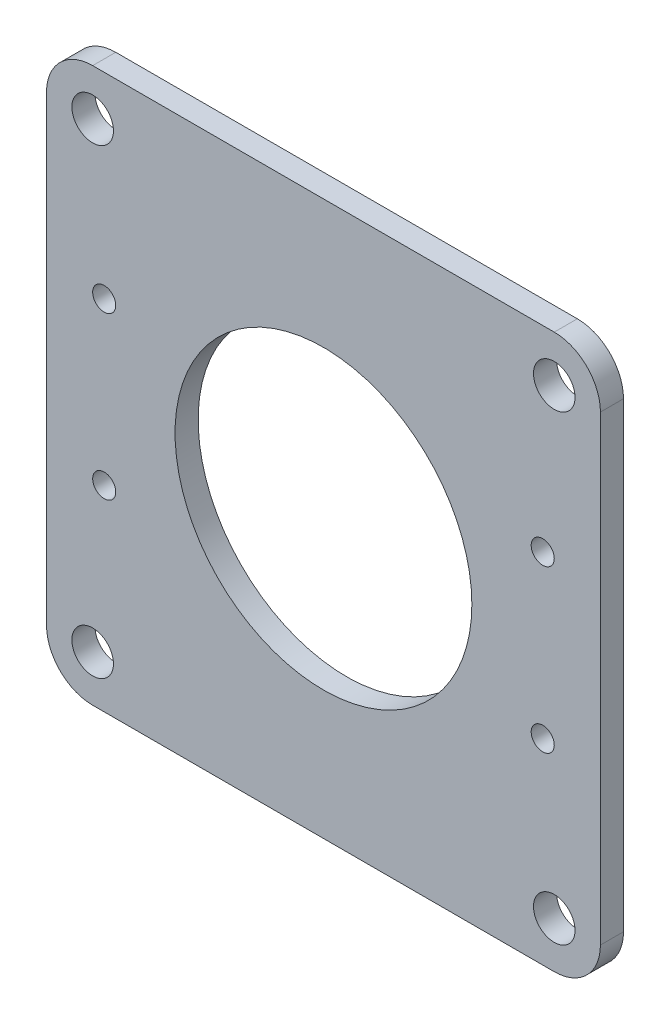
SolidWorks part; units mm, degrees
ref_plane "Front Plane" through (0, 0, 0) normal (0, 0, 1) x (1, 0, 0)
ref_plane "Top Plane" through (0, 0, 0) normal (0, 1, 0) x (1, 0, 0)
ref_plane "Right Plane" through (0, 0, 0) normal (1, 0, 0) x (0, 0, -1)
sketch "Model" plane through (0, 0, 0) normal (0, 0, 1) x (1, 0, 0)
  line L0 (80.983, 843.7421) -> (65.983, 843.7421)
  line L1 (30.983, 843.7421) -> (30.983, 993.7421)
  line L2 (45.983, 993.7421) -> (30.983, 993.7421)
  line L3 (47.983, 998.7421) -> (45.983, 996.7421)
  line L4 (47.983, 998.7421) -> (63.983, 998.7421)
  line L5 (65.983, 996.7421) -> (65.983, 993.7421)
  line L6 (45.983, 993.7421) -> (45.983, 996.7421)
  line L7 (45.983, 843.7421) -> (30.983, 843.7421)
  line L8 (80.983, 843.7421) -> (80.983, 993.7421)
  line L9 (65.983, 996.7421) -> (63.983, 998.7421)
  line L10 (80.983, 993.7421) -> (65.983, 993.7421)
  line L11 (65.983, 835.7421) -> (65.983, 843.7421)
  line L12 (45.983, 835.7421) -> (47.983, 833.7421)
  line L13 (63.983, 833.7421) -> (65.983, 835.7421)
  line L14 (63.983, 833.7421) -> (47.983, 833.7421)
  line L15 (45.983, 843.7421) -> (45.983, 835.7421)
  line L16 (63.4792, 562.0753) -> (47.4792, 562.0753)
  line L17 (45.4792, 564.0753) -> (47.4792, 562.0753)
  line L18 (45.4792, 572.0753) -> (45.4792, 564.0753)
  line L19 (80.4792, 572.0753) -> (65.4792, 572.0753)
  line L20 (45.4792, 572.0753) -> (30.4792, 572.0753)
  line L21 (80.4792, 572.0753) -> (80.4792, 722.0753)
  line L22 (65.4792, 725.0753) -> (63.4792, 727.0753)
  line L23 (65.4792, 725.0753) -> (65.4792, 722.0753)
  line L24 (80.4792, 722.0753) -> (65.4792, 722.0753)
  line L25 (45.4792, 722.0753) -> (30.4792, 722.0753)
  line L26 (45.4792, 722.0753) -> (45.4792, 725.0753)
  line L27 (63.4792, 562.0753) -> (65.4792, 564.0753)
  line L28 (30.4792, 572.0753) -> (30.4792, 722.0753)
  line L29 (47.4792, 727.0753) -> (45.4792, 725.0753)
  line L30 (47.4792, 727.0753) -> (63.4792, 727.0753)
  line L31 (65.4792, 564.0753) -> (65.4792, 572.0753)
  line L32 (-372.5225, 514.5401) -> (-370.5225, 512.5401)
  line L33 (-316.5225, 514.5401) -> (-314.5225, 512.5401)
  line L34 (-290.5225, 512.5401) -> (-288.5225, 514.5401)
  line L35 (-234.5225, 512.5401) -> (-232.5225, 514.5401)
  line L36 (-260.5225, 514.5401) -> (-258.5225, 512.5401)
  line L37 (-314.5225, 512.5401) -> (-290.5225, 512.5401)
  line L38 (-370.5225, 512.5401) -> (-346.5225, 512.5401)
  line L39 (-258.5225, 512.5401) -> (-234.5225, 512.5401)
  line L40 (-232.5225, 675.5401) -> (-234.5225, 677.5401)
  line L41 (-258.5225, 677.5401) -> (-260.5225, 675.5401)
  line L42 (-288.5225, 675.5401) -> (-290.5225, 677.5401)
  line L43 (-314.5225, 677.5401) -> (-316.5225, 675.5401)
  line L44 (-344.5225, 675.5401) -> (-346.5225, 677.5401)
  line L45 (-370.5225, 677.5401) -> (-372.5225, 675.5401)
  line L46 (-234.5225, 677.5401) -> (-258.5225, 677.5401)
  line L47 (-346.5225, 677.5401) -> (-370.5225, 677.5401)
  line L48 (-290.5225, 677.5401) -> (-314.5225, 677.5401)
  line L49 (-316.5225, 522.5401) -> (-316.5225, 514.5401)
  line L50 (-288.5225, 514.5401) -> (-288.5225, 522.5401)
  line L51 (-260.5225, 522.5401) -> (-260.5225, 514.5401)
  line L52 (-344.5225, 514.5401) -> (-344.5225, 522.5401)
  line L53 (-260.5225, 672.5401) -> (-288.5225, 672.5401)
  line L54 (-316.5225, 672.5401) -> (-344.5225, 672.5401)
  line L55 (-344.5225, 522.5401) -> (-316.5225, 522.5401)
  line L56 (-288.5225, 522.5401) -> (-260.5225, 522.5401)
  line L57 (-288.5225, 672.5401) -> (-288.5225, 675.5401)
  line L58 (-316.5225, 675.5401) -> (-316.5225, 672.5401)
  line L59 (-344.5225, 672.5401) -> (-344.5225, 675.5401)
  line L60 (-260.5225, 675.5401) -> (-260.5225, 672.5401)
  line L61 (-232.5225, 514.5401) -> (-232.5225, 675.5401)
  line L62 (-372.5225, 675.5401) -> (-372.5225, 514.5401)
  line L63 (-346.5225, 512.5401) -> (-344.5225, 514.5401)
  line L64 (-59.6771, 563.4465) -> (-59.6771, 571.4465)
  line L65 (-85.6771, 561.4465) -> (-61.6771, 561.4465)
  line L66 (-87.6771, 571.4465) -> (-87.6771, 563.4465)
  line L67 (-115.6771, 571.4465) -> (-87.6771, 571.4465)
  line L68 (-115.6771, 563.4465) -> (-115.6771, 571.4465)
  line L69 (-141.6771, 561.4465) -> (-117.6771, 561.4465)
  line L70 (-143.6771, 724.4465) -> (-143.6771, 563.4465)
  line L71 (-141.6771, 726.4465) -> (-143.6771, 724.4465)
  line L72 (-117.6771, 726.4465) -> (-141.6771, 726.4465)
  line L73 (-115.6771, 724.4465) -> (-117.6771, 726.4465)
  line L74 (-115.6771, 721.4465) -> (-115.6771, 724.4465)
  line L75 (-87.6771, 721.4465) -> (-115.6771, 721.4465)
  line L76 (-87.6771, 724.4465) -> (-87.6771, 721.4465)
  line L77 (-85.6771, 726.4465) -> (-87.6771, 724.4465)
  line L78 (-61.6771, 726.4465) -> (-85.6771, 726.4465)
  line L79 (-59.6771, 724.4465) -> (-61.6771, 726.4465)
  line L80 (-59.6771, 721.4465) -> (-59.6771, 724.4465)
  line L81 (-31.6771, 721.4465) -> (-59.6771, 721.4465)
  line L82 (-31.6771, 724.4465) -> (-31.6771, 721.4465)
  line L83 (-29.6771, 726.4465) -> (-31.6771, 724.4465)
  line L84 (-5.6771, 726.4465) -> (-29.6771, 726.4465)
  line L85 (-3.6771, 724.4465) -> (-5.6771, 726.4465)
  line L86 (-3.6771, 563.4465) -> (-3.6771, 724.4465)
  line L87 (-5.6771, 561.4465) -> (-3.6771, 563.4465)
  line L88 (-29.6771, 561.4465) -> (-5.6771, 561.4465)
  line L89 (-31.6771, 563.4465) -> (-29.6771, 561.4465)
  line L90 (-31.6771, 571.4465) -> (-31.6771, 563.4465)
  line L91 (-59.6771, 571.4465) -> (-31.6771, 571.4465)
  line L92 (-117.6771, 561.4465) -> (-115.6771, 563.4465)
  line L93 (-143.6771, 563.4465) -> (-141.6771, 561.4465)
  line L94 (-87.6771, 563.4465) -> (-85.6771, 561.4465)
  line L95 (-61.6771, 561.4465) -> (-59.6771, 563.4465)
  line L96 (-53.1392, 838.5777) -> (-53.1392, 846.5777)
  line L97 (-55.1392, 836.5777) -> (-53.1392, 838.5777)
  line L98 (-79.1392, 836.5777) -> (-55.1392, 836.5777)
  line L99 (-81.1392, 838.5777) -> (-79.1392, 836.5777)
  line L100 (-81.1392, 846.5777) -> (-81.1392, 838.5777)
  line L101 (-109.1392, 846.5777) -> (-81.1392, 846.5777)
  line L102 (-109.1392, 838.5777) -> (-109.1392, 846.5777)
  line L103 (-135.1392, 836.5777) -> (-111.1392, 836.5777)
  line L104 (-135.1392, 1001.5777) -> (-137.1392, 999.5777)
  line L105 (-111.1392, 1001.5777) -> (-135.1392, 1001.5777)
  line L106 (-109.1392, 999.5777) -> (-111.1392, 1001.5777)
  line L107 (-81.1392, 996.5777) -> (-109.1392, 996.5777)
  line L108 (-81.1392, 999.5777) -> (-81.1392, 996.5777)
  line L109 (-79.1392, 1001.5777) -> (-81.1392, 999.5777)
  line L110 (-55.1392, 1001.5777) -> (-79.1392, 1001.5777)
  line L111 (-53.1392, 999.5777) -> (-55.1392, 1001.5777)
  line L112 (-53.1392, 996.5777) -> (-53.1392, 999.5777)
  line L113 (-25.1392, 996.5777) -> (-53.1392, 996.5777)
  line L114 (-23.1392, 1001.5777) -> (-25.1392, 999.5777)
  line L115 (0.8608, 1001.5777) -> (-23.1392, 1001.5777)
  line L116 (2.8608, 999.5777) -> (0.8608, 1001.5777)
  line L117 (0.8608, 836.5777) -> (2.8608, 838.5777)
  line L118 (-23.1392, 836.5777) -> (0.8608, 836.5777)
  line L119 (-25.1392, 838.5777) -> (-23.1392, 836.5777)
  line L120 (-25.1392, 846.5777) -> (-25.1392, 838.5777)
  line L121 (-53.1392, 846.5777) -> (-25.1392, 846.5777)
  line L122 (-111.1392, 836.5777) -> (-109.1392, 838.5777)
  line L123 (-137.1392, 838.5777) -> (-135.1392, 836.5777)
  line L124 (-109.1392, 996.5777) -> (-109.1392, 999.5777)
  line L125 (-25.1392, 999.5777) -> (-25.1392, 996.5777)
  line L126 (2.8608, 838.5777) -> (2.8608, 999.5777)
  line L127 (-137.1392, 999.5777) -> (-137.1392, 838.5777)
  line L128 (-529.5341, 643.0011) -> (-529.5341, 482.0011)
  line L129 (-501.5341, 640.0011) -> (-501.5341, 643.0011)
  line L130 (-473.5341, 643.0011) -> (-473.5341, 640.0011)
  line L131 (-445.5341, 640.0011) -> (-445.5341, 643.0011)
  line L132 (-417.5341, 643.0011) -> (-417.5341, 640.0011)
  line L133 (-389.5341, 482.0011) -> (-389.5341, 643.0011)
  line L134 (-445.5341, 490.0011) -> (-417.5341, 490.0011)
  line L135 (-503.5341, 480.0011) -> (-501.5341, 482.0011)
  line L136 (-529.5341, 482.0011) -> (-527.5341, 480.0011)
  line L137 (-473.5341, 482.0011) -> (-471.5341, 480.0011)
  line L138 (-447.5341, 480.0011) -> (-445.5341, 482.0011)
  line L139 (-391.5341, 480.0011) -> (-389.5341, 482.0011)
  line L140 (-417.5341, 482.0011) -> (-415.5341, 480.0011)
  line L141 (-471.5341, 480.0011) -> (-447.5341, 480.0011)
  line L142 (-527.5341, 480.0011) -> (-503.5341, 480.0011)
  line L143 (-415.5341, 480.0011) -> (-391.5341, 480.0011)
  line L144 (-389.5341, 643.0011) -> (-391.5341, 645.0011)
  line L145 (-415.5341, 645.0011) -> (-417.5341, 643.0011)
  line L146 (-445.5341, 643.0011) -> (-447.5341, 645.0011)
  line L147 (-471.5341, 645.0011) -> (-473.5341, 643.0011)
  line L148 (-501.5341, 643.0011) -> (-503.5341, 645.0011)
  line L149 (-527.5341, 645.0011) -> (-529.5341, 643.0011)
  line L150 (-391.5341, 645.0011) -> (-415.5341, 645.0011)
  line L151 (-503.5341, 645.0011) -> (-527.5341, 645.0011)
  line L152 (-447.5341, 645.0011) -> (-471.5341, 645.0011)
  line L153 (-473.5341, 490.0011) -> (-473.5341, 482.0011)
  line L154 (-445.5341, 482.0011) -> (-445.5341, 490.0011)
  line L155 (-417.5341, 490.0011) -> (-417.5341, 482.0011)
  line L156 (-501.5341, 482.0011) -> (-501.5341, 490.0011)
  line L157 (-417.5341, 640.0011) -> (-445.5341, 640.0011)
  line L158 (-473.5341, 640.0011) -> (-501.5341, 640.0011)
  line L159 (-501.5341, 490.0011) -> (-473.5341, 490.0011)
  line L160 (-468.249, 439.1114) -> (-496.249, 439.1114)
  line L161 (-468.249, 447.1114) -> (-468.249, 439.1114)
  line L162 (-466.249, 449.1114) -> (-468.249, 447.1114)
  line L163 (-466.249, 449.1114) -> (-442.249, 449.1114)
  line L164 (-440.249, 447.1114) -> (-440.249, 439.1114)
  line L165 (-412.249, 439.1114) -> (-440.249, 439.1114)
  line L166 (-412.249, 447.1114) -> (-412.249, 439.1114)
  line L167 (-410.249, 449.1114) -> (-412.249, 447.1114)
  line L168 (-410.249, 449.1114) -> (-386.249, 449.1114)
  line L169 (-384.249, 447.1114) -> (-386.249, 449.1114)
  line L170 (-384.249, 447.1114) -> (-384.249, 439.1114)
  line L171 (-64.249, 439.1114) -> (-384.249, 439.1114)
  line L172 (-64.249, 447.1114) -> (-64.249, 439.1114)
  line L173 (-62.249, 449.1114) -> (-64.249, 447.1114)
  line L174 (-62.249, 449.1114) -> (-38.249, 449.1114)
  line L175 (-36.249, 447.1114) -> (-38.249, 449.1114)
  line L176 (-36.249, 447.1114) -> (-36.249, 439.1114)
  line L177 (-8.249, 439.1114) -> (-36.249, 439.1114)
  line L178 (-8.249, 447.1114) -> (-8.249, 439.1114)
  line L179 (-6.249, 449.1114) -> (-8.249, 447.1114)
  line L180 (19.751, 447.1114) -> (17.751, 449.1114)
  line L181 (19.751, 447.1114) -> (19.751, 439.1114)
  line L182 (47.751, 439.1114) -> (19.751, 439.1114)
  line L183 (47.751, 447.1114) -> (47.751, 439.1114)
  line L184 (49.751, 449.1114) -> (47.751, 447.1114)
  line L185 (49.751, 449.1114) -> (73.751, 449.1114)
  line L186 (75.751, 447.1114) -> (73.751, 449.1114)
  line L187 (75.751, 447.1114) -> (75.751, 286.1114)
  line L188 (73.751, 284.1114) -> (75.751, 286.1114)
  line L189 (73.751, 284.1114) -> (49.751, 284.1114)
  line L190 (47.751, 286.1114) -> (49.751, 284.1114)
  line L191 (47.751, 289.1114) -> (19.751, 289.1114)
  line L192 (19.751, 286.1114) -> (19.751, 289.1114)
  line L193 (17.751, 284.1114) -> (19.751, 286.1114)
  line L194 (17.751, 284.1114) -> (-6.249, 284.1114)
  line L195 (-8.249, 286.1114) -> (-6.249, 284.1114)
  line L196 (-8.249, 289.1114) -> (-36.249, 289.1114)
  line L197 (-36.249, 286.1114) -> (-36.249, 289.1114)
  line L198 (-38.249, 284.1114) -> (-36.249, 286.1114)
  line L199 (-38.249, 284.1114) -> (-62.249, 284.1114)
  line L200 (-64.249, 286.1114) -> (-62.249, 284.1114)
  line L201 (-64.249, 286.1114) -> (-64.249, 289.1114)
  line L202 (-64.249, 289.1114) -> (-384.249, 289.1114)
  line L203 (-384.249, 286.1114) -> (-384.249, 289.1114)
  line L204 (-386.249, 284.1114) -> (-384.249, 286.1114)
  line L205 (-386.249, 284.1114) -> (-410.249, 284.1114)
  line L206 (-412.249, 286.1114) -> (-410.249, 284.1114)
  line L207 (-412.249, 286.1114) -> (-412.249, 289.1114)
  line L208 (-412.249, 289.1114) -> (-440.249, 289.1114)
  line L209 (-440.249, 286.1114) -> (-440.249, 289.1114)
  line L210 (-442.249, 284.1114) -> (-440.249, 286.1114)
  line L211 (-442.249, 284.1114) -> (-466.249, 284.1114)
  line L212 (-468.249, 286.1114) -> (-466.249, 284.1114)
  line L213 (-468.249, 286.1114) -> (-468.249, 289.1114)
  line L214 (-468.249, 289.1114) -> (-496.249, 289.1114)
  line L215 (-498.249, 284.1114) -> (-496.249, 286.1114)
  line L216 (-498.249, 284.1114) -> (-522.249, 284.1114)
  line L217 (-524.249, 286.1114) -> (-522.249, 284.1114)
  line L218 (-524.249, 286.1114) -> (-524.249, 447.1114)
  line L219 (-522.249, 449.1114) -> (-524.249, 447.1114)
  line L220 (-522.249, 449.1114) -> (-498.249, 449.1114)
  line L221 (-496.249, 447.1114) -> (-496.249, 439.1114)
  line L222 (-64.249, 314.1114) -> (-64.249, 414.1114)
  line L223 (-74.249, 424.1114) -> (-374.249, 424.1114)
  line L224 (-384.249, 314.1114) -> (-384.249, 414.1114)
  line L225 (-374.249, 304.1114) -> (-74.249, 304.1114)
  line L226 (-496.249, 286.1114) -> (-496.249, 289.1114)
  line L227 (-8.249, 286.1114) -> (-8.249, 289.1114)
  line L228 (47.751, 286.1114) -> (47.751, 289.1114)
  line L229 (-6.249, 449.1114) -> (17.751, 449.1114)
  line L230 (-440.249, 447.1114) -> (-442.249, 449.1114)
  line L231 (-496.249, 447.1114) -> (-498.249, 449.1114)
  line L232 (-464.3221, 248.6391) -> (-492.3221, 248.6391)
  line L233 (-464.3221, 256.6391) -> (-464.3221, 248.6391)
  line L234 (-462.3221, 258.6391) -> (-464.3221, 256.6391)
  line L235 (-462.3221, 258.6391) -> (-438.3221, 258.6391)
  line L236 (-436.3221, 256.6391) -> (-438.3221, 258.6391)
  line L237 (-436.3221, 256.6391) -> (-436.3221, 248.6391)
  line L238 (-408.3221, 248.6391) -> (-436.3221, 248.6391)
  line L239 (-408.3221, 256.6391) -> (-408.3221, 248.6391)
  line L240 (-406.3221, 258.6391) -> (-408.3221, 256.6391)
  line L241 (-406.3221, 258.6391) -> (-382.3221, 258.6391)
  line L242 (-380.3221, 256.6391) -> (-382.3221, 258.6391)
  line L243 (-380.3221, 256.6391) -> (-380.3221, 248.6391)
  line L244 (-60.3221, 248.6391) -> (-380.3221, 248.6391)
  line L245 (-60.3221, 256.6391) -> (-60.3221, 248.6391)
  line L246 (-58.3221, 258.6391) -> (-60.3221, 256.6391)
  line L247 (-58.3221, 258.6391) -> (-34.3221, 258.6391)
  line L248 (-32.3221, 256.6391) -> (-34.3221, 258.6391)
  line L249 (-32.3221, 256.6391) -> (-32.3221, 248.6391)
  line L250 (-4.3221, 256.6391) -> (-4.3221, 248.6391)
  line L251 (23.6779, 256.6391) -> (21.6779, 258.6391)
  line L252 (23.6779, 256.6391) -> (23.6779, 248.6391)
  line L253 (51.6779, 256.6391) -> (51.6779, 248.6391)
  line L254 (53.6779, 258.6391) -> (51.6779, 256.6391)
  line L255 (79.6779, 256.6391) -> (77.6779, 258.6391)
  line L256 (79.6779, 256.6391) -> (79.6779, 95.6391)
  line L257 (77.6779, 93.6391) -> (79.6779, 95.6391)
  line L258 (77.6779, 93.6391) -> (53.6779, 93.6391)
  line L259 (51.6779, 95.6391) -> (53.6779, 93.6391)
  line L260 (51.6779, 95.6391) -> (51.6779, 98.6391)
  line L261 (51.6779, 98.6391) -> (23.6779, 98.6391)
  line L262 (23.6779, 95.6391) -> (23.6779, 98.6391)
  line L263 (21.6779, 93.6391) -> (23.6779, 95.6391)
  line L264 (21.6779, 93.6391) -> (-2.3221, 93.6391)
  line L265 (-4.3221, 95.6391) -> (-2.3221, 93.6391)
  line L266 (-4.3221, 95.6391) -> (-4.3221, 98.6391)
  line L267 (-4.3221, 98.6391) -> (-32.3221, 98.6391)
  line L268 (-32.3221, 95.6391) -> (-32.3221, 98.6391)
  line L269 (-34.3221, 93.6391) -> (-32.3221, 95.6391)
  line L270 (-34.3221, 93.6391) -> (-58.3221, 93.6391)
  line L271 (-60.3221, 95.6391) -> (-58.3221, 93.6391)
  line L272 (-60.3221, 95.6391) -> (-60.3221, 98.6391)
  line L273 (-60.3221, 98.6391) -> (-380.3221, 98.6391)
  line L274 (-380.3221, 95.6391) -> (-380.3221, 98.6391)
  line L275 (-382.3221, 93.6391) -> (-380.3221, 95.6391)
  line L276 (-382.3221, 93.6391) -> (-406.3221, 93.6391)
  line L277 (-408.3221, 95.6391) -> (-406.3221, 93.6391)
  line L278 (-408.3221, 95.6391) -> (-408.3221, 98.6391)
  line L279 (-408.3221, 98.6391) -> (-436.3221, 98.6391)
  line L280 (-436.3221, 95.6391) -> (-436.3221, 98.6391)
  line L281 (-438.3221, 93.6391) -> (-462.3221, 93.6391)
  line L282 (-464.3221, 95.6391) -> (-462.3221, 93.6391)
  line L283 (-464.3221, 95.6391) -> (-464.3221, 98.6391)
  line L284 (-464.3221, 98.6391) -> (-492.3221, 98.6391)
  line L285 (-492.3221, 95.6391) -> (-492.3221, 98.6391)
  line L286 (-494.3221, 93.6391) -> (-518.3221, 93.6391)
  line L287 (-520.3221, 95.6391) -> (-518.3221, 93.6391)
  line L288 (-520.3221, 95.6391) -> (-520.3221, 256.6391)
  line L289 (-518.3221, 258.6391) -> (-520.3221, 256.6391)
  line L290 (-518.3221, 258.6391) -> (-494.3221, 258.6391)
  line L291 (-492.3221, 256.6391) -> (-492.3221, 248.6391)
  line L292 (-60.3221, 123.6391) -> (-60.3221, 223.6391)
  line L293 (-70.3221, 233.6391) -> (-370.3221, 233.6391)
  line L294 (-380.3221, 123.6391) -> (-380.3221, 223.6391)
  line L295 (-370.3221, 113.6391) -> (-70.3221, 113.6391)
  line L296 (-492.3221, 256.6391) -> (-494.3221, 258.6391)
  line L297 (51.6779, 248.6391) -> (23.6779, 248.6391)
  line L298 (53.6779, 258.6391) -> (77.6779, 258.6391)
  line L299 (-2.3221, 258.6391) -> (21.6779, 258.6391)
  line L300 (-494.3221, 93.6391) -> (-492.3221, 95.6391)
  line L301 (-4.3221, 248.6391) -> (-32.3221, 248.6391)
  line L302 (-2.3221, 258.6391) -> (-4.3221, 256.6391)
  line L303 (-438.3221, 93.6391) -> (-436.3221, 95.6391)
  line L304 (-213.8187, 967.5429) -> (-219.0187, 967.5429)
  line L305 (-219.0187, 995.3429) -> (-219.0187, 967.5429)
  line L306 (-219.0187, 1051.3429) -> (-219.0187, 1023.5429)
  line L307 (-219.0187, 1051.3429) -> (-213.8187, 1051.3429)
  line L308 (-166.2187, 1079.5429) -> (-213.8187, 1079.5429)
  line L309 (-166.2187, 1079.5429) -> (-166.2187, 1051.3429)
  line L310 (102.9813, 1079.5429) -> (102.9813, 1051.3429)
  line L311 (102.9813, 1051.3429) -> (108.1813, 1051.3429)
  line L312 (108.1813, 1051.3429) -> (108.1813, 1079.5429)
  line L313 (155.7813, 1079.5429) -> (108.1813, 1079.5429)
  line L314 (155.7813, 1079.5429) -> (155.7813, 1051.3429)
  line L315 (155.7813, 1051.3429) -> (160.9813, 1051.3429)
  line L316 (160.9813, 1023.5429) -> (160.9813, 1051.3429)
  line L317 (160.9813, 1023.5429) -> (155.7813, 1023.5429)
  line L318 (155.7813, 1023.5429) -> (155.7813, 995.3429)
  line L319 (155.7813, 995.3429) -> (160.9813, 995.3429)
  line L320 (160.9813, 967.5429) -> (160.9813, 995.3429)
  line L321 (160.9813, 967.5429) -> (155.7813, 967.5429)
  line L322 (155.7813, 967.5429) -> (155.7813, 939.3429)
  line L323 (155.7813, 939.3429) -> (160.9813, 939.3429)
  line L324 (160.9813, 619.7429) -> (160.9813, 939.3429)
  line L325 (160.9813, 619.7429) -> (155.7813, 619.7429)
  line L326 (155.7813, 619.7429) -> (155.7813, 591.5429)
  line L327 (155.7813, 591.5429) -> (160.9813, 591.5429)
  line L328 (160.9813, 563.7429) -> (160.9813, 591.5429)
  line L329 (160.9813, 563.7429) -> (155.7813, 563.7429)
  line L330 (155.7813, 563.7429) -> (155.7813, 535.5429)
  line L331 (155.7813, 535.5429) -> (160.9813, 535.5429)
  line L332 (160.9813, 507.7429) -> (160.9813, 535.5429)
  line L333 (160.9813, 507.7429) -> (155.7813, 507.7429)
  line L334 (155.7813, 507.7429) -> (155.7813, 479.5429)
  line L335 (108.1813, 479.5429) -> (155.7813, 479.5429)
  line L336 (108.1813, 479.5429) -> (108.1813, 507.7429)
  line L337 (108.1813, 507.7429) -> (102.9813, 507.7429)
  line L338 (102.9813, 507.7429) -> (102.9813, 479.5429)
  line L339 (-161.0187, 479.5429) -> (102.9813, 479.5429)
  line L340 (-161.0187, 479.5429) -> (-161.0187, 507.7429)
  line L341 (-161.0187, 507.7429) -> (-166.2187, 507.7429)
  line L342 (-166.2187, 507.7429) -> (-166.2187, 479.5429)
  line L343 (-213.8187, 479.5429) -> (-166.2187, 479.5429)
  line L344 (-213.8187, 507.7429) -> (-219.0187, 507.7429)
  line L345 (-219.0187, 535.5429) -> (-219.0187, 507.7429)
  line L346 (-219.0187, 591.5429) -> (-213.8187, 591.5429)
  line L347 (-213.8187, 591.5429) -> (-213.8187, 619.7429)
  line L348 (-213.8187, 619.7429) -> (-219.0187, 619.7429)
  line L349 (-219.0187, 939.3429) -> (-213.8187, 939.3429)
  line L350 (-166.2187, 591.5429) -> (-161.0187, 591.5429)
  line L351 (-161.0187, 563.7429) -> (-161.0187, 591.5429)
  line L352 (-161.0187, 563.7429) -> (-166.2187, 563.7429)
  line L353 (-166.2187, 535.5429) -> (108.1813, 535.5429)
  line L354 (108.1813, 535.5429) -> (108.1813, 563.7429)
  line L355 (108.1813, 563.7429) -> (102.9813, 563.7429)
  line L356 (102.9813, 591.5429) -> (102.9813, 563.7429)
  line L357 (102.9813, 591.5429) -> (108.1813, 591.5429)
  line L358 (108.1813, 591.5429) -> (108.1813, 619.7429)
  line L359 (108.1813, 619.7429) -> (102.9813, 619.7429)
  line L360 (102.9813, 754.5429) -> (102.9813, 619.7429)
  line L361 (102.9813, 754.5429) -> (-161.0187, 754.5429)
  line L362 (-161.0187, 619.7429) -> (-166.2187, 619.7429)
  line L363 (-166.2187, 619.7429) -> (-166.2187, 591.5429)
  line L364 (108.1813, 967.5429) -> (102.9813, 967.5429)
  line L365 (102.9813, 995.3429) -> (102.9813, 967.5429)
  line L366 (102.9813, 995.3429) -> (108.1813, 995.3429)
  line L367 (108.1813, 995.3429) -> (108.1813, 1023.5429)
  line L368 (108.1813, 1023.5429) -> (-166.2187, 1023.5429)
  line L369 (-166.2187, 995.3429) -> (-161.0187, 995.3429)
  line L370 (-161.0187, 967.5429) -> (-161.0187, 995.3429)
  line L371 (-161.0187, 967.5429) -> (-166.2187, 967.5429)
  line L372 (-166.2187, 939.3429) -> (-161.0187, 939.3429)
  line L373 (-161.0187, 804.5429) -> (-161.0187, 939.3429)
  line L374 (-161.0187, 804.5429) -> (102.9813, 804.5429)
  line L375 (102.9813, 939.3429) -> (102.9813, 804.5429)
  line L376 (102.9813, 939.3429) -> (108.1813, 939.3429)
  line L377 (108.1813, 939.3429) -> (108.1813, 967.5429)
  line L378 (102.7813, 789.7429) -> (108.1813, 789.7429)
  line L379 (102.7813, 769.3429) -> (102.7813, 789.7429)
  line L380 (108.1813, 769.3429) -> (102.7813, 769.3429)
  line L381 (108.1813, 769.3429) -> (108.1813, 789.7429)
  line L382 (-166.2187, 1023.5429) -> (-166.2187, 995.3429)
  line L383 (-161.0187, 1051.3429) -> (-161.0187, 1079.5429)
  line L384 (-219.0187, 535.5429) -> (-213.8187, 535.5429)
  line L385 (-213.8187, 479.5429) -> (-213.8187, 507.7429)
  line L386 (-166.2187, 563.7429) -> (-166.2187, 535.5429)
  line L387 (-213.8187, 535.5429) -> (-213.8187, 563.7429)
  line L388 (-219.0187, 939.3429) -> (-219.0187, 619.7429)
  line L389 (-219.0187, 591.5429) -> (-219.0187, 563.7429)
  line L390 (-166.2187, 789.7429) -> (-166.2187, 769.3429)
  line L391 (-160.8187, 789.7429) -> (-160.8187, 769.3429)
  line L392 (-160.8187, 769.3429) -> (-166.2187, 769.3429)
  line L393 (-166.2187, 789.7429) -> (-160.8187, 789.7429)
  line L394 (-213.8187, 1051.3429) -> (-213.8187, 1079.5429)
  line L395 (-166.2187, 967.5429) -> (-166.2187, 939.3429)
  line L396 (-213.8187, 995.3429) -> (-213.8187, 1023.5429)
  line L397 (-213.8187, 939.3429) -> (-213.8187, 967.5429)
  line L398 (-219.0187, 995.3429) -> (-213.8187, 995.3429)
  line L399 (-213.8187, 1023.5429) -> (-219.0187, 1023.5429)
  line L400 (-166.2187, 1051.3429) -> (-161.0187, 1051.3429)
  line L401 (102.9813, 1079.5429) -> (-161.0187, 1079.5429)
  line L402 (-161.0187, 619.7429) -> (-161.0187, 754.5429)
  line L403 (-213.8187, 563.7429) -> (-219.0187, 563.7429)
  line L404 (-870.316, 286.3663) -> (-870.316, 376.1663)
  line L405 (-860.316, 276.3663) -> (-616.316, 276.3663)
  line L406 (-606.316, 376.1663) -> (-606.316, 286.3663)
  line L407 (-606.316, 376.1663) -> (-601.116, 376.1663)
  line L408 (-601.116, 376.1663) -> (-601.116, 396.5663)
  line L409 (-601.116, 396.5663) -> (-606.316, 396.5663)
  line L410 (-606.316, 416.3663) -> (-606.316, 396.5663)
  line L411 (-616.316, 426.3663) -> (-860.316, 426.3663)
  line L412 (-870.316, 396.5663) -> (-870.316, 416.3663)
  line L413 (-870.316, 396.5663) -> (-875.516, 396.5663)
  line L414 (-875.516, 396.5663) -> (-875.516, 376.1663)
  line L415 (-875.516, 376.1663) -> (-870.316, 376.1663)
  line L416 (-870.116, 602.1663) -> (-870.116, 630.5663)
  line L417 (-870.116, 630.5663) -> (-875.516, 630.5701)
  line L418 (-875.516, 630.5701) -> (-875.516, 602.1663)
  line L419 (-875.516, 602.1663) -> (-870.116, 602.1663)
  line L420 (-870.116, 546.1663) -> (-870.116, 574.5663)
  line L421 (-870.116, 574.5663) -> (-875.516, 574.5663)
  line L422 (-875.516, 574.5663) -> (-875.516, 546.1663)
  line L423 (-875.516, 546.1663) -> (-870.116, 546.1663)
  line L424 (-870.116, 198.1663) -> (-870.116, 226.5663)
  line L425 (-870.116, 226.5663) -> (-875.516, 226.5663)
  line L426 (-875.516, 226.5663) -> (-875.516, 198.1663)
  line L427 (-875.516, 198.1663) -> (-870.116, 198.1663)
  line L428 (-606.516, 630.5663) -> (-606.516, 602.1663)
  line L429 (-606.516, 602.1663) -> (-601.116, 602.1663)
  line L430 (-601.116, 602.1663) -> (-601.116, 630.5701)
  line L431 (-601.116, 630.5701) -> (-606.516, 630.5663)
  line L432 (-606.516, 574.5663) -> (-606.516, 546.1663)
  line L433 (-606.516, 546.1663) -> (-601.116, 546.1663)
  line L434 (-601.116, 546.1663) -> (-601.116, 574.5663)
  line L435 (-601.116, 574.5663) -> (-606.516, 574.5663)
  line L436 (-606.516, 226.5663) -> (-606.516, 198.1663)
  line L437 (-606.516, 198.1663) -> (-601.116, 198.1663)
  line L438 (-601.116, 198.1663) -> (-601.116, 226.5663)
  line L439 (-601.116, 226.5663) -> (-606.516, 226.5663)
  line L440 (-606.516, 170.5663) -> (-606.516, 142.1663)
  line L441 (-606.516, 142.1663) -> (-601.116, 142.1626)
  line L442 (-601.116, 142.1626) -> (-601.116, 170.5663)
  line L443 (-601.116, 170.5663) -> (-606.516, 170.5663)
  line L444 (-870.116, 142.1663) -> (-870.116, 170.5663)
  line L445 (-870.116, 170.5663) -> (-875.516, 170.5663)
  line L446 (-875.516, 170.5663) -> (-875.516, 142.1626)
  line L447 (-875.516, 142.1626) -> (-870.116, 142.1663)
  line L448 (-601.116, 86.3663) -> (-553.516, 86.3663)
  line L449 (-601.116, 86.3663) -> (-601.116, 114.5663)
  line L450 (-601.116, 114.5663) -> (-606.516, 114.5663)
  line L451 (-606.516, 114.5663) -> (-606.516, 86.3663)
  line L452 (-870.116, 86.3663) -> (-606.516, 86.3663)
  line L453 (-870.116, 86.3663) -> (-870.116, 114.5663)
  line L454 (-870.116, 114.5663) -> (-875.516, 114.5663)
  line L455 (-875.516, 114.5663) -> (-875.516, 86.3663)
  line L456 (-923.116, 86.3663) -> (-875.516, 86.3663)
  line L457 (-923.116, 86.3663) -> (-923.116, 114.5663)
  line L458 (-923.116, 114.5663) -> (-928.316, 114.5663)
  line L459 (-928.316, 142.1662) -> (-928.316, 114.5663)
  line L460 (-928.316, 142.1662) -> (-923.116, 142.1626)
  line L461 (-923.116, 142.1626) -> (-923.116, 170.5663)
  line L462 (-923.116, 170.5663) -> (-928.316, 170.5663)
  line L463 (-928.316, 198.1663) -> (-928.316, 170.5663)
  line L464 (-928.316, 198.1663) -> (-923.116, 198.1663)
  line L465 (-923.116, 198.1663) -> (-923.116, 226.5663)
  line L466 (-923.116, 226.5663) -> (-928.316, 226.5663)
  line L467 (-928.316, 546.1663) -> (-928.316, 226.5663)
  line L468 (-923.116, 546.1663) -> (-928.316, 546.1663)
  line L469 (-923.116, 546.1663) -> (-923.116, 574.5663)
  line L470 (-928.316, 574.5663) -> (-923.116, 574.5663)
  line L471 (-928.316, 602.1663) -> (-928.316, 574.5663)
  line L472 (-923.116, 602.1663) -> (-928.316, 602.1663)
  line L473 (-923.116, 602.1663) -> (-923.116, 630.5701)
  line L474 (-923.116, 630.5701) -> (-928.316, 630.5665)
  line L475 (-928.316, 658.1663) -> (-928.316, 630.5665)
  line L476 (-923.116, 658.1663) -> (-928.316, 658.1663)
  line L477 (-923.116, 658.1663) -> (-923.116, 686.3663)
  line L478 (-875.516, 686.3663) -> (-923.116, 686.3663)
  line L479 (-875.516, 686.3663) -> (-875.516, 658.1663)
  line L480 (-875.516, 658.1663) -> (-870.116, 658.1663)
  line L481 (-870.116, 658.1663) -> (-870.116, 686.3663)
  line L482 (-606.516, 686.3663) -> (-870.116, 686.3663)
  line L483 (-606.516, 686.3663) -> (-606.516, 658.1663)
  line L484 (-606.516, 658.1663) -> (-601.116, 658.1663)
  line L485 (-601.116, 658.1663) -> (-601.116, 686.3663)
  line L486 (-553.516, 686.3663) -> (-601.116, 686.3663)
  line L487 (-553.516, 686.3663) -> (-553.516, 658.1663)
  line L488 (-553.516, 658.1663) -> (-548.316, 658.1663)
  line L489 (-548.316, 630.5665) -> (-548.316, 658.1663)
  line L490 (-548.316, 630.5665) -> (-553.516, 630.5701)
  line L491 (-553.516, 630.5701) -> (-553.516, 602.1663)
  line L492 (-553.516, 602.1663) -> (-548.316, 602.1663)
  line L493 (-548.316, 574.5663) -> (-548.316, 602.1663)
  line L494 (-548.316, 574.5663) -> (-553.516, 574.5663)
  line L495 (-553.516, 574.5663) -> (-553.516, 546.1663)
  line L496 (-553.516, 546.1663) -> (-548.316, 546.1663)
  line L497 (-548.316, 226.5663) -> (-548.316, 546.1663)
  line L498 (-553.516, 226.5663) -> (-548.316, 226.5663)
  line L499 (-553.516, 226.5663) -> (-553.516, 198.1663)
  line L500 (-548.316, 198.1663) -> (-553.516, 198.1663)
  line L501 (-548.316, 170.5663) -> (-548.316, 198.1663)
  line L502 (-553.516, 170.5663) -> (-548.316, 170.5663)
  line L503 (-553.516, 170.5663) -> (-553.516, 142.1626)
  line L504 (-553.516, 142.1626) -> (-548.316, 142.1662)
  line L505 (-548.316, 114.5663) -> (-548.316, 142.1662)
  line L506 (-553.516, 114.5663) -> (-548.316, 114.5663)
  line L507 (-553.516, 114.5663) -> (-553.516, 86.3663)
  line L508 (-822.6094, 703.4061) -> (-822.6094, 708.6061)
  line L509 (-850.2094, 703.4061) -> (-822.6094, 703.4061)
  line L510 (-850.2094, 708.5061) -> (-850.2094, 703.4061)
  line L511 (-878.6094, 708.6061) -> (-850.2094, 708.5061)
  line L512 (-878.6094, 703.5758) -> (-878.6094, 708.6061)
  line L513 (-911.5094, 759.4061) -> (-878.6094, 703.5758)
  line L514 (-911.5094, 1027.4061) -> (-911.5094, 759.4061)
  line L515 (-878.6094, 1083.2364) -> (-911.5094, 1027.4061)
  line L516 (-878.6094, 1083.2364) -> (-878.6094, 1078.2061)
  line L517 (-878.6094, 1078.2061) -> (-850.2094, 1078.3061)
  line L518 (-850.2094, 1078.3061) -> (-850.2094, 1083.4061)
  line L519 (-822.6094, 1083.4061) -> (-822.6094, 1078.2061)
  line L520 (-822.6094, 1078.2061) -> (-794.2094, 1078.3061)
  line L521 (-794.2094, 1078.3061) -> (-794.2094, 1083.4061)
  line L522 (-766.6094, 1083.4061) -> (-766.6094, 1078.2061)
  line L523 (-766.6094, 1078.2061) -> (-738.2094, 1078.2061)
  line L524 (-738.2094, 1078.2061) -> (-738.2094, 1083.4061)
  line L525 (-418.8094, 1078.2061) -> (-418.8094, 1083.4061)
  line L526 (-390.4094, 1078.2061) -> (-418.8094, 1078.2061)
  line L527 (-390.4094, 1083.4061) -> (-390.4094, 1078.2061)
  line L528 (-362.8094, 1083.4061) -> (-390.4094, 1083.4061)
  line L529 (-362.8094, 1078.3061) -> (-362.8094, 1083.4061)
  line L530 (-334.4094, 1078.2061) -> (-362.8094, 1078.3061)
  line L531 (-334.4094, 1083.4061) -> (-334.4094, 1078.2061)
  line L532 (-306.8094, 1083.4061) -> (-334.4094, 1083.4061)
  line L533 (-306.8094, 1078.3061) -> (-306.8094, 1083.4061)
  line L534 (-278.4094, 1078.2061) -> (-306.8094, 1078.3061)
  line L535 (-278.4094, 1083.2364) -> (-278.4094, 1078.2061)
  line L536 (-245.5094, 1027.4061) -> (-278.4094, 1083.2364)
  line L537 (-245.5094, 759.4061) -> (-245.5094, 1027.4061)
  line L538 (-278.4094, 703.5758) -> (-245.5094, 759.4061)
  line L539 (-278.4094, 703.5758) -> (-278.4094, 708.6061)
  line L540 (-278.4094, 708.6061) -> (-306.8094, 708.5061)
  line L541 (-306.8094, 708.5061) -> (-306.8094, 703.4061)
  line L542 (-334.4094, 703.4061) -> (-334.4094, 708.6061)
  line L543 (-334.4094, 708.6061) -> (-362.8094, 708.5061)
  line L544 (-362.8094, 708.5061) -> (-362.8094, 703.4061)
  line L545 (-390.4094, 703.4061) -> (-390.4094, 708.6061)
  line L546 (-390.4094, 708.6061) -> (-418.8094, 708.6061)
  line L547 (-418.8094, 708.6061) -> (-418.8094, 703.4061)
  line L548 (-738.2094, 708.6061) -> (-738.2094, 703.4061)
  line L549 (-766.6094, 708.6061) -> (-738.2094, 708.6061)
  line L550 (-766.6094, 703.4061) -> (-766.6094, 708.6061)
  line L551 (-794.2094, 703.4061) -> (-766.6094, 703.4061)
  line L552 (-794.2094, 708.5061) -> (-794.2094, 703.4061)
  line L553 (-822.6094, 708.6061) -> (-794.2094, 708.5061)
  line L554 (-794.2094, 761.5061) -> (-794.2094, 756.2061)
  line L555 (-822.6094, 761.5061) -> (-794.2094, 761.5061)
  line L556 (-822.6094, 756.1061) -> (-822.6094, 761.5061)
  line L557 (-822.6094, 756.1061) -> (-794.2094, 756.2061)
  line L558 (-362.8094, 1025.3061) -> (-362.8094, 1030.6061)
  line L559 (-334.4094, 1025.3061) -> (-362.8094, 1025.3061)
  line L560 (-334.4094, 1030.7061) -> (-334.4094, 1025.3061)
  line L561 (-334.4094, 1030.7061) -> (-362.8094, 1030.6061)
  line L562 (-568.3094, 756.2061) -> (-568.3094, 761.6061)
  line L563 (-568.3094, 761.6061) -> (-588.7094, 761.6061)
  line L564 (-588.7094, 761.6061) -> (-588.7094, 756.2061)
  line L565 (-588.7094, 756.2061) -> (-568.3094, 756.2061)
  line L566 (-418.8094, 1025.3061) -> (-418.8094, 1030.7061)
  line L567 (-390.4094, 1025.3061) -> (-418.8094, 1025.3061)
  line L568 (-390.4094, 1030.7061) -> (-390.4094, 1025.3061)
  line L569 (-390.4094, 1030.7061) -> (-418.8094, 1030.7061)
  line L570 (-278.4094, 761.5061) -> (-278.4094, 756.1061)
  line L571 (-306.8094, 761.5061) -> (-278.4094, 761.5061)
  line L572 (-306.8094, 756.2061) -> (-306.8094, 761.5061)
  line L573 (-278.4094, 756.1061) -> (-306.8094, 756.2061)
  line L574 (-334.4094, 761.5061) -> (-334.4094, 756.1061)
  line L575 (-362.8094, 761.5061) -> (-334.4094, 761.5061)
  line L576 (-362.8094, 756.2061) -> (-362.8094, 761.5061)
  line L577 (-334.4094, 756.1061) -> (-362.8094, 756.2061)
  line L578 (-390.4094, 761.5061) -> (-390.4094, 756.1061)
  line L579 (-418.8094, 761.5061) -> (-390.4094, 761.5061)
  line L580 (-418.8094, 756.1061) -> (-418.8094, 761.5061)
  line L581 (-390.4094, 756.1061) -> (-418.8094, 756.1061)
  line L582 (-766.6094, 1025.3061) -> (-766.6094, 1030.7061)
  line L583 (-738.2094, 1025.3061) -> (-766.6094, 1025.3061)
  line L584 (-738.2094, 1030.7061) -> (-738.2094, 1025.3061)
  line L585 (-766.6094, 1030.7061) -> (-738.2094, 1030.7061)
  line L586 (-822.6094, 1025.3061) -> (-822.6094, 1030.7061)
  line L587 (-794.2094, 1025.3061) -> (-822.6094, 1025.3061)
  line L588 (-794.2094, 1030.6061) -> (-794.2094, 1025.3061)
  line L589 (-822.6094, 1030.7061) -> (-794.2094, 1030.6061)
  line L590 (-878.6094, 1025.3061) -> (-878.6094, 1030.7061)
  line L591 (-850.2094, 1025.3061) -> (-878.6094, 1025.3061)
  line L592 (-878.6094, 1030.7061) -> (-850.2094, 1030.6061)
  line L593 (-588.7094, 1030.6061) -> (-588.7094, 1025.2061)
  line L594 (-588.7094, 1025.2061) -> (-568.3094, 1025.2061)
  line L595 (-568.3094, 1025.2061) -> (-568.3094, 1030.6061)
  line L596 (-588.7094, 1030.6061) -> (-568.3094, 1030.6061)
  line L597 (-306.8094, 1025.3061) -> (-306.8094, 1030.6061)
  line L598 (-278.4094, 1025.3061) -> (-306.8094, 1025.3061)
  line L599 (-278.4094, 1030.7061) -> (-278.4094, 1025.3061)
  line L600 (-278.4094, 1030.7061) -> (-306.8094, 1030.6061)
  line L601 (-738.2094, 761.5061) -> (-738.2094, 756.1061)
  line L602 (-766.6094, 761.5061) -> (-738.2094, 761.5061)
  line L603 (-766.6094, 756.1061) -> (-766.6094, 761.5061)
  line L604 (-766.6094, 756.1061) -> (-738.2094, 756.1061)
  line L605 (-850.2094, 761.5061) -> (-850.2094, 756.2061)
  line L606 (-878.6094, 761.5061) -> (-850.2094, 761.5061)
  line L607 (-878.6094, 756.1061) -> (-878.6094, 761.5061)
  line L608 (-878.6094, 756.1061) -> (-850.2094, 756.2061)
  line L609 (-334.4094, 703.4061) -> (-306.8094, 703.4061)
  line L610 (-418.8094, 1083.4061) -> (-738.2094, 1083.4061)
  line L611 (-850.2094, 1030.6061) -> (-850.2094, 1025.3061)
  line L612 (-738.2094, 703.4061) -> (-418.8094, 703.4061)
  line L613 (-390.4094, 703.4061) -> (-362.8094, 703.4061)
  line L614 (-822.6094, 1083.4061) -> (-850.2094, 1083.4061)
  line L615 (-766.6094, 1083.4061) -> (-794.2094, 1083.4061)
  circle A0 centre (-302.5225, 597.5401) radius 39
  circle A1 centre (-73.6771, 646.4465) radius 39
  circle A2 centre (-67.1392, 921.5777) radius 39
  circle A3 centre (-459.5341, 565.0011) radius 39
  circle A4 centre (5.751, 364.1114) radius 39
  circle A5 centre (-454.249, 364.1114) radius 39
  circle A6 centre (-504.249, 414.1114) radius 4.5
  circle A7 centre (-504.249, 314.1114) radius 4.5
  circle A8 centre (-404.249, 414.1114) radius 4.5
  circle A9 centre (-404.249, 314.1114) radius 4.5
  circle A10 centre (-44.249, 314.1114) radius 4.5
  circle A11 centre (-44.249, 414.1114) radius 4.5
  circle A12 centre (55.751, 314.1114) radius 4.5
  circle A13 centre (55.751, 414.1114) radius 4.5
  circle A14 centre (-501.749, 381.6114) radius 2.5
  circle A15 centre (-406.749, 381.6114) radius 2.5
  circle A16 centre (-406.749, 346.6114) radius 2.5
  circle A17 centre (-501.749, 346.6114) radius 2.5
  circle A18 centre (53.251, 381.6114) radius 2.5
  circle A19 centre (-41.749, 381.6114) radius 2.5
  circle A20 centre (-41.749, 346.6114) radius 2.5
  circle A21 centre (53.251, 346.6114) radius 2.5
  circle A22 centre (9.6779, 173.6391) radius 39
  circle A23 centre (-450.3221, 173.6391) radius 39
  circle A24 centre (-500.3221, 223.6391) radius 4.5
  circle A25 centre (-500.3221, 123.6391) radius 4.5
  circle A26 centre (-400.3221, 223.6391) radius 4.5
  circle A27 centre (-400.3221, 123.6391) radius 4.5
  circle A28 centre (-40.3221, 123.6391) radius 4.5
  circle A29 centre (-40.3221, 223.6391) radius 4.5
  circle A30 centre (59.6779, 123.6391) radius 4.5
  circle A31 centre (59.6779, 223.6391) radius 4.5
  circle A32 centre (-497.8221, 191.1391) radius 2.5
  circle A33 centre (-402.8221, 191.1391) radius 2.5
  circle A34 centre (-402.8221, 156.1391) radius 2.5
  circle A35 centre (-497.8221, 156.1391) radius 2.5
  circle A36 centre (57.1779, 191.1391) radius 2.5
  circle A37 centre (-37.8221, 191.1391) radius 2.5
  circle A38 centre (-37.8221, 156.1391) radius 2.5
  circle A39 centre (57.1779, 156.1391) radius 2.5
  circle A40 centre (131.9813, 779.5429) radius 2.6
  circle A41 centre (134.0813, 507.5429) radius 2.6
  circle A42 centre (134.0813, 1051.5429) radius 2.6
  circle A43 centre (-192.1187, 1051.5429) radius 2.6
  circle A44 centre (-190.0187, 779.5429) radius 2.6
  circle A45 centre (-192.1187, 507.5429) radius 2.6
  circle A46 centre (-837.316, 105.3663) radius 3.6
  circle A47 centre (-639.316, 499.3663) radius 3.6
  circle A48 centre (-837.316, 556.3663) radius 3.6
  circle A49 centre (-815.316, 556.3663) radius 3.6
  circle A50 centre (-661.316, 537.3663) radius 3.6
  circle A51 centre (-727.316, 499.3663) radius 3.6
  circle A52 centre (-837.316, 518.3663) radius 3.6
  circle A53 centre (-815.316, 518.3663) radius 3.6
  circle A54 centre (-661.316, 499.3663) radius 3.6
  circle A55 centre (-771.316, 556.3663) radius 3.6
  circle A56 centre (-793.316, 537.3663) radius 3.6
  circle A57 centre (-771.316, 537.3663) radius 3.6
  circle A58 centre (-837.316, 537.3663) radius 3.6
  circle A59 centre (-639.316, 537.3663) radius 3.6
  circle A60 centre (-749.316, 556.3663) radius 3.6
  circle A61 centre (-727.316, 556.3663) radius 3.6
  circle A62 centre (-793.316, 556.3663) radius 3.6
  circle A63 centre (-683.316, 594.3663) radius 3.6
  circle A64 centre (-749.316, 518.3663) radius 3.6
  circle A65 centre (-727.316, 518.3663) radius 3.6
  circle A66 centre (-793.316, 518.3663) radius 3.6
  circle A67 centre (-771.316, 594.3663) radius 3.6
  circle A68 centre (-661.316, 594.3663) radius 3.6
  circle A69 centre (-639.316, 594.3663) radius 3.6
  circle A70 centre (-705.316, 594.3663) radius 3.6
  circle A71 centre (-683.316, 518.3663) radius 3.6
  circle A72 centre (-705.316, 499.3663) radius 3.6
  circle A73 centre (-683.316, 499.3663) radius 3.6
  circle A74 centre (-749.316, 499.3663) radius 3.6
  circle A75 centre (-771.316, 518.3663) radius 3.6
  circle A76 centre (-661.316, 518.3663) radius 3.6
  circle A77 centre (-639.316, 518.3663) radius 3.6
  circle A78 centre (-705.316, 518.3663) radius 3.6
  circle A79 centre (-771.316, 632.3663) radius 3.6
  circle A80 centre (-749.316, 670.3663) radius 3.6
  circle A81 centre (-727.316, 670.3663) radius 3.6
  circle A82 centre (-793.316, 670.3663) radius 3.6
  circle A83 centre (-639.316, 613.3663) radius 3.6
  circle A84 centre (-749.316, 632.3663) radius 3.6
  circle A85 centre (-727.316, 632.3663) radius 3.6
  circle A86 centre (-793.316, 632.3663) radius 3.6
  circle A87 centre (-683.316, 670.3663) radius 3.6
  circle A88 centre (-705.316, 651.3663) radius 3.6
  circle A89 centre (-683.316, 651.3663) radius 3.6
  circle A90 centre (-749.316, 651.3663) radius 3.6
  circle A91 centre (-661.316, 670.3663) radius 3.6
  circle A92 centre (-639.316, 670.3663) radius 3.6
  circle A93 centre (-705.316, 670.3663) radius 3.6
  circle A94 centre (-727.316, 537.3663) radius 3.6
  circle A95 centre (-661.316, 632.3663) radius 3.6
  circle A96 centre (-639.316, 632.3663) radius 3.6
  circle A97 centre (-705.316, 632.3663) radius 3.6
  circle A98 centre (-815.316, 537.3663) radius 3.6
  circle A99 centre (-705.316, 537.3663) radius 3.6
  circle A100 centre (-683.316, 537.3663) radius 3.6
  circle A101 centre (-749.316, 537.3663) radius 3.6
  circle A102 centre (-815.316, 651.3663) radius 3.6
  circle A103 centre (-837.316, 632.3663) radius 3.6
  circle A104 centre (-815.316, 632.3663) radius 3.6
  circle A105 centre (-661.316, 613.3663) radius 3.6
  circle A106 centre (-683.316, 632.3663) radius 3.6
  circle A107 centre (-793.316, 651.3663) radius 3.6
  circle A108 centre (-749.316, 594.3663) radius 3.6
  circle A109 centre (-727.316, 613.3663) radius 3.6
  circle A110 centre (-837.316, 575.3663) radius 3.6
  circle A111 centre (-771.316, 575.3663) radius 3.6
  circle A112 centre (-793.316, 575.3663) radius 3.6
  circle A113 centre (-683.316, 556.3663) radius 3.6
  circle A114 centre (-837.316, 613.3663) radius 3.6
  circle A115 centre (-771.316, 613.3663) radius 3.6
  circle A116 centre (-793.316, 613.3663) radius 3.6
  circle A117 centre (-815.316, 575.3663) radius 3.6
  circle A118 centre (-661.316, 480.3663) radius 3.6
  circle A119 centre (-639.316, 480.3663) radius 3.6
  circle A120 centre (-705.316, 480.3663) radius 3.6
  circle A121 centre (-683.316, 480.3663) radius 3.6
  circle A122 centre (-793.316, 499.3663) radius 3.6
  circle A123 centre (-771.316, 499.3663) radius 3.6
  circle A124 centre (-837.316, 499.3663) radius 3.6
  circle A125 centre (-815.316, 499.3663) radius 3.6
  circle A126 centre (-771.316, 480.3663) radius 3.6
  circle A127 centre (-793.316, 480.3663) radius 3.6
  circle A128 centre (-727.316, 480.3663) radius 3.6
  circle A129 centre (-749.316, 480.3663) radius 3.6
  circle A130 centre (-639.316, 461.3663) radius 3.6
  circle A131 centre (-661.316, 461.3663) radius 3.6
  circle A132 centre (-815.316, 480.3663) radius 3.6
  circle A133 centre (-837.316, 480.3663) radius 3.6
  circle A134 centre (-683.316, 442.3663) radius 3.6
  circle A135 centre (-705.316, 442.3663) radius 3.6
  circle A136 centre (-639.316, 442.3663) radius 3.6
  circle A137 centre (-661.316, 442.3663) radius 3.6
  circle A138 centre (-771.316, 442.3663) radius 3.6
  circle A139 centre (-793.316, 442.3663) radius 3.6
  circle A140 centre (-727.316, 442.3663) radius 3.6
  circle A141 centre (-749.316, 442.3663) radius 3.6
  circle A142 centre (-749.316, 461.3663) radius 3.6
  circle A143 centre (-683.316, 461.3663) radius 3.6
  circle A144 centre (-705.316, 461.3663) radius 3.6
  circle A145 centre (-815.316, 461.3663) radius 3.6
  circle A146 centre (-837.316, 461.3663) radius 3.6
  circle A147 centre (-771.316, 461.3663) radius 3.6
  circle A148 centre (-793.316, 461.3663) radius 3.6
  circle A149 centre (-639.316, 200.3663) radius 3.6
  circle A150 centre (-639.316, 219.3663) radius 3.6
  circle A151 centre (-639.316, 162.3663) radius 3.6
  circle A152 centre (-639.316, 181.3663) radius 3.6
  circle A153 centre (-837.316, 442.3663) radius 3.6
  circle A154 centre (-815.316, 442.3663) radius 3.6
  circle A155 centre (-639.316, 238.3663) radius 3.6
  circle A156 centre (-639.316, 257.3663) radius 3.6
  circle A157 centre (-639.316, 124.3663) radius 3.6
  circle A158 centre (-639.316, 143.3663) radius 3.6
  circle A159 centre (-661.316, 257.3663) radius 3.6
  circle A160 centre (-639.316, 105.3663) radius 3.6
  circle A161 centre (-661.316, 200.3663) radius 3.6
  circle A162 centre (-661.316, 181.3663) radius 3.6
  circle A163 centre (-661.316, 238.3663) radius 3.6
  circle A164 centre (-661.316, 219.3663) radius 3.6
  circle A165 centre (-683.316, 238.3663) radius 3.6
  circle A166 centre (-683.316, 257.3663) radius 3.6
  circle A167 centre (-683.316, 200.3663) radius 3.6
  circle A168 centre (-683.316, 219.3663) radius 3.6
  circle A169 centre (-661.316, 143.3663) radius 3.6
  circle A170 centre (-661.316, 162.3663) radius 3.6
  circle A171 centre (-661.316, 105.3663) radius 3.6
  circle A172 centre (-661.316, 124.3663) radius 3.6
  circle A173 centre (-683.316, 143.3663) radius 3.6
  circle A174 centre (-683.316, 124.3663) radius 3.6
  circle A175 centre (-683.316, 181.3663) radius 3.6
  circle A176 centre (-705.316, 257.3663) radius 3.6
  circle A177 centre (-683.316, 105.3663) radius 3.6
  circle A178 centre (-705.316, 219.3663) radius 3.6
  circle A179 centre (-705.316, 238.3663) radius 3.6
  circle A180 centre (-771.316, 219.3663) radius 3.6
  circle A181 centre (-705.316, 105.3663) radius 3.6
  circle A182 centre (-705.316, 124.3663) radius 3.6
  circle A183 centre (-727.316, 238.3663) radius 3.6
  circle A184 centre (-771.316, 143.3663) radius 3.6
  circle A185 centre (-771.316, 238.3663) radius 3.6
  circle A186 centre (-771.316, 257.3663) radius 3.6
  circle A187 centre (-771.316, 200.3663) radius 3.6
  circle A188 centre (-705.316, 162.3663) radius 3.6
  circle A189 centre (-727.316, 124.3663) radius 3.6
  circle A190 centre (-727.316, 143.3663) radius 3.6
  circle A191 centre (-749.316, 257.3663) radius 3.6
  circle A192 centre (-727.316, 257.3663) radius 3.6
  circle A193 centre (-705.316, 181.3663) radius 3.6
  circle A194 centre (-705.316, 200.3663) radius 3.6
  circle A195 centre (-705.316, 143.3663) radius 3.6
  circle A196 centre (-639.316, 651.3663) radius 3.6
  circle A197 centre (-749.316, 143.3663) radius 3.6
  circle A198 centre (-749.316, 162.3663) radius 3.6
  circle A199 centre (-749.316, 105.3663) radius 3.6
  circle A200 centre (-727.316, 651.3663) radius 3.6
  circle A201 centre (-837.316, 670.3663) radius 3.6
  circle A202 centre (-815.316, 670.3663) radius 3.6
  circle A203 centre (-661.316, 651.3663) radius 3.6
  circle A204 centre (-749.316, 200.3663) radius 3.6
  circle A205 centre (-771.316, 162.3663) radius 3.6
  circle A206 centre (-771.316, 181.3663) radius 3.6
  circle A207 centre (-771.316, 124.3663) radius 3.6
  circle A208 centre (-749.316, 124.3663) radius 3.6
  circle A209 centre (-749.316, 219.3663) radius 3.6
  circle A210 centre (-749.316, 181.3663) radius 3.6
  circle A211 centre (-793.316, 257.3663) radius 3.6
  circle A212 centre (-771.316, 105.3663) radius 3.6
  circle A213 centre (-793.316, 219.3663) radius 3.6
  circle A214 centre (-793.316, 238.3663) radius 3.6
  circle A215 centre (-793.316, 162.3663) radius 3.6
  circle A216 centre (-793.316, 143.3663) radius 3.6
  circle A217 centre (-793.316, 200.3663) radius 3.6
  circle A218 centre (-793.316, 181.3663) radius 3.6
  circle A219 centre (-815.316, 257.3663) radius 3.6
  circle A220 centre (-815.316, 238.3663) radius 3.6
  circle A221 centre (-793.316, 124.3663) radius 3.6
  circle A222 centre (-793.316, 105.3663) radius 3.6
  circle A223 centre (-815.316, 181.3663) radius 3.6
  circle A224 centre (-815.316, 162.3663) radius 3.6
  circle A225 centre (-815.316, 219.3663) radius 3.6
  circle A226 centre (-815.316, 200.3663) radius 3.6
  circle A227 centre (-727.316, 181.3663) radius 3.6
  circle A228 centre (-837.316, 219.3663) radius 3.6
  circle A229 centre (-837.316, 238.3663) radius 3.6
  circle A230 centre (-837.316, 181.3663) radius 3.6
  circle A231 centre (-727.316, 105.3663) radius 3.6
  circle A232 centre (-727.316, 200.3663) radius 3.6
  circle A233 centre (-727.316, 219.3663) radius 3.6
  circle A234 centre (-727.316, 162.3663) radius 3.6
  circle A235 centre (-815.316, 105.3663) radius 3.6
  circle A236 centre (-837.316, 143.3663) radius 3.6
  circle A237 centre (-837.316, 162.3663) radius 3.6
  circle A238 centre (-837.316, 124.3663) radius 3.6
  circle A239 centre (-837.316, 200.3663) radius 3.6
  circle A240 centre (-815.316, 124.3663) radius 3.6
  circle A241 centre (-815.316, 143.3663) radius 3.6
  circle A242 centre (-837.316, 257.3663) radius 3.6
  circle A243 centre (-749.316, 238.3663) radius 3.6
  circle A244 centre (-683.316, 162.3663) radius 3.6
  circle A245 centre (-639.316, 575.3663) radius 3.6
  circle A246 centre (-661.316, 556.3663) radius 3.6
  circle A247 centre (-727.316, 575.3663) radius 3.6
  circle A248 centre (-837.316, 594.3663) radius 3.6
  circle A249 centre (-815.316, 594.3663) radius 3.6
  circle A250 centre (-771.316, 651.3663) radius 3.6
  circle A251 centre (-727.316, 461.3663) radius 3.6
  circle A252 centre (-705.316, 556.3663) radius 3.6
  circle A253 centre (-661.316, 575.3663) radius 3.6
  circle A254 centre (-639.316, 556.3663) radius 3.6
  circle A255 centre (-793.316, 594.3663) radius 3.6
  circle A256 centre (-705.316, 613.3663) radius 3.6
  circle A257 centre (-705.316, 575.3663) radius 3.6
  circle A258 centre (-837.316, 651.3663) radius 3.6
  circle A259 centre (-771.316, 670.3663) radius 3.6
  circle A260 centre (-727.316, 594.3663) radius 3.6
  circle A261 centre (-749.316, 575.3663) radius 3.6
  circle A262 centre (-815.316, 613.3663) radius 3.6
  circle A263 centre (-683.316, 575.3663) radius 3.6
  circle A264 centre (-749.316, 613.3663) radius 3.6
  circle A265 centre (-683.316, 613.3663) radius 3.6
  circle A266 centre (-272.0094, 739.4061) radius 3.6
  circle A267 centre (-254.5094, 761.4061) radius 3.6
  circle A268 centre (-254.5094, 1025.4061) radius 3.6
  circle A269 centre (-272.0094, 1047.4061) radius 3.6
  circle A270 centre (-885.0094, 1047.4061) radius 3.6
  circle A271 centre (-902.5094, 1025.4061) radius 3.6
  circle A272 centre (-902.5094, 761.4061) radius 3.6
  circle A273 centre (-885.0094, 739.4061) radius 3.6
  circle A274 centre (-661.0094, 937.4061) radius 3.6
  circle A275 centre (-661.0094, 871.4061) radius 3.6
  circle A276 centre (-661.0094, 893.4061) radius 3.6
  circle A277 centre (-272.0094, 871.4061) radius 3.6
  circle A278 centre (-661.0094, 849.4061) radius 3.6
  circle A279 centre (-661.0094, 783.4061) radius 3.6
  circle A280 centre (-661.0094, 805.4061) radius 3.6
  circle A281 centre (-661.0094, 915.4061) radius 3.6
  circle A282 centre (-254.5094, 1003.4061) radius 3.6
  circle A283 centre (-272.0094, 827.4061) radius 3.6
  circle A284 centre (-272.0094, 805.4061) radius 3.6
  circle A285 centre (-272.0094, 849.4061) radius 3.6
  circle A286 centre (-272.0094, 915.4061) radius 3.6
  circle A287 centre (-272.0094, 893.4061) radius 3.6
  circle A288 centre (-272.0094, 783.4061) radius 3.6
  circle A289 centre (-639.0094, 827.4061) radius 3.6
  circle A290 centre (-617.0094, 1003.4061) radius 3.6
  circle A291 centre (-639.0094, 783.4061) radius 3.6
  circle A292 centre (-661.0094, 1003.4061) radius 3.6
  circle A293 centre (-617.0094, 981.4061) radius 3.6
  circle A294 centre (-617.0094, 915.4061) radius 3.6
  circle A295 centre (-617.0094, 937.4061) radius 3.6
  circle A296 centre (-639.0094, 805.4061) radius 3.6
  circle A297 centre (-683.0094, 871.4061) radius 3.6
  circle A298 centre (-683.0094, 805.4061) radius 3.6
  circle A299 centre (-683.0094, 827.4061) radius 3.6
  circle A300 centre (-683.0094, 783.4061) radius 3.6
  circle A301 centre (-661.0094, 959.4061) radius 3.6
  circle A302 centre (-661.0094, 981.4061) radius 3.6
  circle A303 centre (-683.0094, 849.4061) radius 3.6
  circle A304 centre (-254.5094, 827.4061) radius 3.6
  circle A305 centre (-254.5094, 893.4061) radius 3.6
  circle A306 centre (-254.5094, 871.4061) radius 3.6
  circle A307 centre (-386.0094, 1003.4061) radius 3.6
  circle A308 centre (-254.5094, 915.4061) radius 3.6
  circle A309 centre (-254.5094, 981.4061) radius 3.6
  circle A310 centre (-254.5094, 959.4061) radius 3.6
  circle A311 centre (-254.5094, 849.4061) radius 3.6
  circle A312 centre (-386.0094, 893.4061) radius 3.6
  circle A313 centre (-386.0094, 959.4061) radius 3.6
  circle A314 centre (-386.0094, 937.4061) radius 3.6
  circle A315 centre (-364.0094, 937.4061) radius 3.6
  circle A316 centre (-386.0094, 981.4061) radius 3.6
  circle A317 centre (-364.0094, 805.4061) radius 3.6
  circle A318 centre (-364.0094, 783.4061) radius 3.6
  circle A319 centre (-386.0094, 915.4061) radius 3.6
  circle A320 centre (-272.0094, 937.4061) radius 3.6
  circle A321 centre (-272.0094, 1003.4061) radius 3.6
  circle A322 centre (-272.0094, 981.4061) radius 3.6
  circle A323 centre (-617.0094, 783.4061) radius 3.6
  circle A324 centre (-540.0094, 805.4061) radius 3.6
  circle A325 centre (-540.0094, 783.4061) radius 3.6
  circle A326 centre (-272.0094, 959.4061) radius 3.6
  circle A327 centre (-617.0094, 893.4061) radius 3.6
  circle A328 centre (-617.0094, 827.4061) radius 3.6
  circle A329 centre (-617.0094, 849.4061) radius 3.6
  circle A330 centre (-254.5094, 937.4061) radius 3.6
  circle A331 centre (-617.0094, 805.4061) radius 3.6
  circle A332 centre (-254.5094, 805.4061) radius 3.6
  circle A333 centre (-254.5094, 783.4061) radius 3.6
  circle A334 centre (-617.0094, 871.4061) radius 3.6
  circle A335 centre (-430.0094, 783.4061) radius 3.6
  circle A336 centre (-518.0094, 827.4061) radius 3.6
  circle A337 centre (-540.0094, 1003.4061) radius 3.6
  circle A338 centre (-518.0094, 849.4061) radius 3.6
  circle A339 centre (-518.0094, 915.4061) radius 3.6
  circle A340 centre (-518.0094, 893.4061) radius 3.6
  circle A341 centre (-518.0094, 783.4061) radius 3.6
  circle A342 centre (-452.0094, 915.4061) radius 3.6
  circle A343 centre (-452.0094, 981.4061) radius 3.6
  circle A344 centre (-452.0094, 959.4061) radius 3.6
  circle A345 centre (-430.0094, 959.4061) radius 3.6
  circle A346 centre (-452.0094, 1003.4061) radius 3.6
  circle A347 centre (-430.0094, 827.4061) radius 3.6
  circle A348 centre (-430.0094, 805.4061) radius 3.6
  circle A349 centre (-452.0094, 937.4061) radius 3.6
  circle A350 centre (-496.0094, 871.4061) radius 3.6
  circle A351 centre (-496.0094, 937.4061) radius 3.6
  circle A352 centre (-496.0094, 915.4061) radius 3.6
  circle A353 centre (-540.0094, 937.4061) radius 3.6
  circle A354 centre (-496.0094, 959.4061) radius 3.6
  circle A355 centre (-474.0094, 783.4061) radius 3.6
  circle A356 centre (-496.0094, 1003.4061) radius 3.6
  circle A357 centre (-496.0094, 893.4061) radius 3.6
  circle A358 centre (-540.0094, 827.4061) radius 3.6
  circle A359 centre (-540.0094, 893.4061) radius 3.6
  circle A360 centre (-540.0094, 871.4061) radius 3.6
  circle A361 centre (-518.0094, 871.4061) radius 3.6
  circle A362 centre (-540.0094, 915.4061) radius 3.6
  circle A363 centre (-540.0094, 981.4061) radius 3.6
  circle A364 centre (-540.0094, 959.4061) radius 3.6
  circle A365 centre (-540.0094, 849.4061) radius 3.6
  circle A366 centre (-474.0094, 981.4061) radius 3.6
  circle A367 centre (-452.0094, 805.4061) radius 3.6
  circle A368 centre (-452.0094, 783.4061) radius 3.6
  circle A369 centre (-639.0094, 893.4061) radius 3.6
  circle A370 centre (-452.0094, 893.4061) radius 3.6
  circle A371 centre (-452.0094, 871.4061) radius 3.6
  circle A372 centre (-474.0094, 1003.4061) radius 3.6
  circle A373 centre (-639.0094, 1003.4061) radius 3.6
  circle A374 centre (-639.0094, 937.4061) radius 3.6
  circle A375 centre (-639.0094, 959.4061) radius 3.6
  circle A376 centre (-617.0094, 959.4061) radius 3.6
  circle A377 centre (-639.0094, 915.4061) radius 3.6
  circle A378 centre (-639.0094, 849.4061) radius 3.6
  circle A379 centre (-639.0094, 871.4061) radius 3.6
  circle A380 centre (-639.0094, 981.4061) radius 3.6
  circle A381 centre (-430.0094, 915.4061) radius 3.6
  circle A382 centre (-430.0094, 893.4061) radius 3.6
  circle A383 centre (-474.0094, 915.4061) radius 3.6
  circle A384 centre (-430.0094, 937.4061) radius 3.6
  circle A385 centre (-430.0094, 1003.4061) radius 3.6
  circle A386 centre (-430.0094, 981.4061) radius 3.6
  circle A387 centre (-430.0094, 871.4061) radius 3.6
  circle A388 centre (-474.0094, 805.4061) radius 3.6
  circle A389 centre (-474.0094, 871.4061) radius 3.6
  circle A390 centre (-474.0094, 849.4061) radius 3.6
  circle A391 centre (-452.0094, 849.4061) radius 3.6
  circle A392 centre (-474.0094, 893.4061) radius 3.6
  circle A393 centre (-474.0094, 959.4061) radius 3.6
  circle A394 centre (-474.0094, 937.4061) radius 3.6
  circle A395 centre (-474.0094, 827.4061) radius 3.6
  circle A396 centre (-683.0094, 981.4061) radius 3.6
  circle A397 centre (-683.0094, 1003.4061) radius 3.6
  circle A398 centre (-727.0094, 981.4061) radius 3.6
  circle A399 centre (-727.0094, 1003.4061) radius 3.6
  circle A400 centre (-727.0094, 937.4061) radius 3.6
  circle A401 centre (-727.0094, 959.4061) radius 3.6
  circle A402 centre (-749.0094, 827.4061) radius 3.6
  circle A403 centre (-705.0094, 1003.4061) radius 3.6
  circle A404 centre (-727.0094, 783.4061) radius 3.6
  circle A405 centre (-727.0094, 893.4061) radius 3.6
  circle A406 centre (-727.0094, 915.4061) radius 3.6
  circle A407 centre (-727.0094, 827.4061) radius 3.6
  circle A408 centre (-727.0094, 805.4061) radius 3.6
  circle A409 centre (-749.0094, 805.4061) radius 3.6
  circle A410 centre (-749.0094, 783.4061) radius 3.6
  circle A411 centre (-705.0094, 981.4061) radius 3.6
  circle A412 centre (-705.0094, 849.4061) radius 3.6
  circle A413 centre (-705.0094, 827.4061) radius 3.6
  circle A414 centre (-705.0094, 893.4061) radius 3.6
  circle A415 centre (-705.0094, 871.4061) radius 3.6
  circle A416 centre (-793.0094, 849.4061) radius 3.6
  circle A417 centre (-793.0094, 827.4061) radius 3.6
  circle A418 centre (-705.0094, 805.4061) radius 3.6
  circle A419 centre (-705.0094, 783.4061) radius 3.6
  circle A420 centre (-683.0094, 915.4061) radius 3.6
  circle A421 centre (-683.0094, 893.4061) radius 3.6
  circle A422 centre (-683.0094, 959.4061) radius 3.6
  circle A423 centre (-683.0094, 937.4061) radius 3.6
  circle A424 centre (-705.0094, 937.4061) radius 3.6
  circle A425 centre (-705.0094, 915.4061) radius 3.6
  circle A426 centre (-885.0094, 1003.4061) radius 3.6
  circle A427 centre (-885.0094, 959.4061) radius 3.6
  circle A428 centre (-885.0094, 915.4061) radius 3.6
  circle A429 centre (-885.0094, 893.4061) radius 3.6
  circle A430 centre (-885.0094, 981.4061) radius 3.6
  circle A431 centre (-885.0094, 937.4061) radius 3.6
  circle A432 centre (-815.0094, 959.4061) radius 3.6
  circle A433 centre (-815.0094, 937.4061) radius 3.6
  circle A434 centre (-885.0094, 827.4061) radius 3.6
  circle A435 centre (-885.0094, 805.4061) radius 3.6
  circle A436 centre (-815.0094, 893.4061) radius 3.6
  circle A437 centre (-902.5094, 893.4061) radius 3.6
  circle A438 centre (-902.5094, 871.4061) radius 3.6
  circle A439 centre (-408.0094, 959.4061) radius 3.6
  circle A440 centre (-386.0094, 783.4061) radius 3.6
  circle A441 centre (-408.0094, 1003.4061) radius 3.6
  circle A442 centre (-342.0094, 871.4061) radius 3.6
  circle A443 centre (-386.0094, 805.4061) radius 3.6
  circle A444 centre (-386.0094, 871.4061) radius 3.6
  circle A445 centre (-386.0094, 849.4061) radius 3.6
  circle A446 centre (-408.0094, 981.4061) radius 3.6
  circle A447 centre (-364.0094, 1003.4061) radius 3.6
  circle A448 centre (-342.0094, 827.4061) radius 3.6
  circle A449 centre (-342.0094, 805.4061) radius 3.6
  circle A450 centre (-342.0094, 959.4061) radius 3.6
  circle A451 centre (-342.0094, 849.4061) radius 3.6
  circle A452 centre (-342.0094, 915.4061) radius 3.6
  circle A453 centre (-342.0094, 783.4061) radius 3.6
  circle A454 centre (-364.0094, 827.4061) radius 3.6
  circle A455 centre (-364.0094, 893.4061) radius 3.6
  circle A456 centre (-364.0094, 871.4061) radius 3.6
  circle A457 centre (-408.0094, 893.4061) radius 3.6
  circle A458 centre (-364.0094, 915.4061) radius 3.6
  circle A459 centre (-364.0094, 981.4061) radius 3.6
  circle A460 centre (-364.0094, 959.4061) radius 3.6
  circle A461 centre (-364.0094, 849.4061) radius 3.6
  circle A462 centre (-408.0094, 783.4061) radius 3.6
  circle A463 centre (-408.0094, 849.4061) radius 3.6
  circle A464 centre (-408.0094, 827.4061) radius 3.6
  circle A465 centre (-386.0094, 827.4061) radius 3.6
  circle A466 centre (-408.0094, 871.4061) radius 3.6
  circle A467 centre (-408.0094, 937.4061) radius 3.6
  circle A468 centre (-408.0094, 915.4061) radius 3.6
  circle A469 centre (-408.0094, 805.4061) radius 3.6
  circle A470 centre (-749.0094, 959.4061) radius 3.6
  circle A471 centre (-749.0094, 981.4061) radius 3.6
  circle A472 centre (-793.0094, 959.4061) radius 3.6
  circle A473 centre (-793.0094, 981.4061) radius 3.6
  circle A474 centre (-793.0094, 915.4061) radius 3.6
  circle A475 centre (-793.0094, 937.4061) radius 3.6
  circle A476 centre (-815.0094, 805.4061) radius 3.6
  circle A477 centre (-815.0094, 827.4061) radius 3.6
  circle A478 centre (-793.0094, 893.4061) radius 3.6
  circle A479 centre (-793.0094, 871.4061) radius 3.6
  circle A480 centre (-771.0094, 1003.4061) radius 3.6
  circle A481 centre (-771.0094, 981.4061) radius 3.6
  circle A482 centre (-793.0094, 1003.4061) radius 3.6
  circle A483 centre (-815.0094, 783.4061) radius 3.6
  circle A484 centre (-793.0094, 783.4061) radius 3.6
  circle A485 centre (-793.0094, 805.4061) radius 3.6
  circle A486 centre (-771.0094, 959.4061) radius 3.6
  circle A487 centre (-771.0094, 827.4061) radius 3.6
  circle A488 centre (-771.0094, 805.4061) radius 3.6
  circle A489 centre (-771.0094, 871.4061) radius 3.6
  circle A490 centre (-771.0094, 849.4061) radius 3.6
  circle A491 centre (-342.0094, 981.4061) radius 3.6
  circle A492 centre (-342.0094, 937.4061) radius 3.6
  circle A493 centre (-749.0094, 871.4061) radius 3.6
  circle A494 centre (-749.0094, 893.4061) radius 3.6
  circle A495 centre (-749.0094, 1003.4061) radius 3.6
  circle A496 centre (-771.0094, 783.4061) radius 3.6
  circle A497 centre (-749.0094, 937.4061) radius 3.6
  circle A498 centre (-749.0094, 915.4061) radius 3.6
  circle A499 centre (-771.0094, 915.4061) radius 3.6
  circle A500 centre (-771.0094, 893.4061) radius 3.6
  circle A501 centre (-496.0094, 805.4061) radius 3.6
  circle A502 centre (-518.0094, 937.4061) radius 3.6
  circle A503 centre (-518.0094, 1003.4061) radius 3.6
  circle A504 centre (-518.0094, 981.4061) radius 3.6
  circle A505 centre (-496.0094, 981.4061) radius 3.6
  circle A506 centre (-496.0094, 783.4061) radius 3.6
  circle A507 centre (-496.0094, 849.4061) radius 3.6
  circle A508 centre (-496.0094, 827.4061) radius 3.6
  circle A509 centre (-518.0094, 959.4061) radius 3.6
  circle A510 centre (-342.0094, 1003.4061) radius 3.6
  circle A511 centre (-850.0666, 730.0773) radius 2.6
  circle A512 centre (-306.0666, 730.0773) radius 2.6
  circle A513 centre (-578.0666, 732.0773) radius 2.6
  circle A514 centre (-306.0666, 1056.0773) radius 2.6
  circle A515 centre (-578.0666, 1054.0773) radius 2.6
  circle A516 centre (-850.0666, 1056.0773) radius 2.6
  circle A517 centre (-518.0094, 805.4061) radius 3.6
  circle A518 centre (-452.0094, 827.4061) radius 3.6
  circle A519 centre (-749.0094, 849.4061) radius 3.6
  circle A520 centre (-885.0094, 871.4061) radius 3.6
  circle A521 centre (-885.0094, 849.4061) radius 3.6
  circle A522 centre (-902.5094, 1003.4061) radius 3.6
  circle A523 centre (-885.0094, 783.4061) radius 3.6
  circle A524 centre (-902.5094, 981.4061) radius 3.6
  circle A525 centre (-902.5094, 959.4061) radius 3.6
  circle A526 centre (-902.5094, 937.4061) radius 3.6
  circle A527 centre (-902.5094, 915.4061) radius 3.6
  circle A528 centre (-902.5094, 805.4061) radius 3.6
  circle A529 centre (-902.5094, 783.4061) radius 3.6
  circle A530 centre (-902.5094, 849.4061) radius 3.6
  circle A531 centre (-902.5094, 827.4061) radius 3.6
  circle A532 centre (-727.0094, 871.4061) radius 3.6
  circle A533 centre (-727.0094, 849.4061) radius 3.6
  circle A534 centre (-815.0094, 1003.4061) radius 3.6
  circle A535 centre (-815.0094, 981.4061) radius 3.6
  circle A536 centre (-815.0094, 871.4061) radius 3.6
  circle A537 centre (-815.0094, 849.4061) radius 3.6
  circle A538 centre (-815.0094, 915.4061) radius 3.6
  circle A539 centre (-342.0094, 893.4061) radius 3.6
  circle A540 centre (-661.0094, 827.4061) radius 3.6
  circle A541 centre (-705.0094, 959.4061) radius 3.6
  circle A542 centre (-771.0094, 937.4061) radius 3.6
  circle A543 centre (-430.0094, 849.4061) radius 3.6
  arc A544 (-74.249, 304.1114) -> (-64.249, 314.1114) centre (-74.249, 314.1114) ccw
  arc A545 (-64.249, 414.1114) -> (-74.249, 424.1114) centre (-74.249, 414.1114) ccw
  arc A546 (-374.249, 424.1114) -> (-384.249, 414.1114) centre (-374.249, 414.1114) ccw
  arc A547 (-384.249, 314.1114) -> (-374.249, 304.1114) centre (-374.249, 314.1114) ccw
  arc A548 (-70.3221, 113.6391) -> (-60.3221, 123.6391) centre (-70.3221, 123.6391) ccw
  arc A549 (-60.3221, 223.6391) -> (-70.3221, 233.6391) centre (-70.3221, 223.6391) ccw
  arc A550 (-370.3221, 233.6391) -> (-380.3221, 223.6391) centre (-370.3221, 223.6391) ccw
  arc A551 (-380.3221, 123.6391) -> (-370.3221, 113.6391) centre (-370.3221, 123.6391) ccw
  arc A552 (-870.316, 286.3663) -> (-860.316, 276.3663) centre (-860.316, 286.3663) ccw
  arc A553 (-616.316, 276.3663) -> (-606.316, 286.3663) centre (-616.316, 286.3663) ccw
  arc A554 (-606.316, 416.3663) -> (-616.316, 426.3663) centre (-616.316, 416.3663) ccw
  arc A555 (-860.316, 426.3663) -> (-870.316, 416.3663) centre (-860.316, 416.3663) ccw
sketch "Sketch2" plane through (0, 0, 0) normal (0, 0, 1) x (1, 0, 0)
  line L0 (-60.3221, 233.6391) -> (79.6779, 233.6391)
  line L1 (79.6779, 256.6391) -> (79.6779, 95.6391) construction
  line L2 (-60.3221, 113.6391) -> (79.6779, 113.6391)
  line L3 (79.6779, 113.6391) -> (79.6779, 233.6391)
  line L4 (-60.3221, 223.6391) -> (-60.3221, 233.6391)
  line L5 (-60.3221, 233.6391) -> (-60.3221, 113.6391)
  circle A0 centre (9.6779, 173.6391) radius 39
  circle A1 centre (-40.3221, 223.6391) radius 4.5
  circle A2 centre (59.6779, 223.6391) radius 4.5
  circle A3 centre (57.1779, 191.1391) radius 2.5
  circle A4 centre (57.1779, 156.1391) radius 2.5
  circle A5 centre (59.6779, 123.6391) radius 4.5
  circle A6 centre (-40.3221, 123.6391) radius 4.5
  circle A7 centre (-37.8221, 156.1391) radius 2.5
  circle A8 centre (-37.8221, 191.1391) radius 2.5
extrude "Boss-Extrude1" add sketch "Sketch2" along normal blind 5 contours L4 L5 L2 L3 L0 A8 A7 A6 A5 A4 A3 A2 A1 A0 region at (9.6779, 231.7952, 0)
sketch "Sketch3" plane through (0, 0, 5) normal (0, 0, 1) x (1, 0, 0)
  circle A0 centre (9.6779, 173.6391) radius 39 construction
  circle A1 centre (9.6779, 173.6391) radius 39
  circle A2 centre (9.6779, 173.6391) radius 32.15
  dimension "D1" = 64.3
extrude "Boss-Extrude2" add sketch "Sketch3" against normal up to surface (5 mm away) up to face at (-35.3221, 191.1391, 0)
sketch "Sketch4" plane through (0, 0, 5) normal (0, 0, 1) x (1, 0, 0)
  line L0 (-60.3221, 233.6391) -> (79.6779, 233.6391) construction
  line L2 (69.6779, 113.6391) -> (69.6779, 233.6391)
  line L4 (-50.3221, 113.6391) -> (-50.3221, 233.6391)
  line L7 (-50.3221, 233.6391) -> (-60.3221, 233.6391)
  line L10 (69.6779, 113.6391) -> (79.6779, 113.6391)
  line L11 (-60.3221, 233.6391) -> (-60.3221, 113.6391)
  line L12 (-60.3221, 113.6391) -> (79.6779, 113.6391)
  line L13 (79.6779, 113.6391) -> (79.6779, 233.6391)
  line L14 (79.6779, 233.6391) -> (-60.3221, 233.6391)
  line L15 (-60.3221, 233.6391) -> (-60.3221, 113.6391)
  line L16 (-60.3221, 113.6391) -> (-50.3221, 113.6391)
  line L17 (79.6779, 113.6391) -> (79.6779, 233.6391)
  line L18 (79.6779, 233.6391) -> (69.6779, 233.6391)
  dimension "D1" = 120
  dimension "D2" = 0
extrude "Cut-Extrude1" cut sketch "Sketch4" against normal through all
sketch "Sketch5" plane through (0, 0, 5) normal (0, 0, 1) x (1, 0, 0)
  line L0 (9.6779, 205.7891) -> (9.6779, 141.4891) construction
  circle A0 centre (9.6779, 173.6391) radius 32.15 construction
fillet "Fillet1" radius 10 4 edges at (-50.3221, 113.6391, 2.5) (69.6779, 113.6391, 2.5) (69.6779, 233.6391, 2.5) (-50.3221, 233.6391, 2.5)
